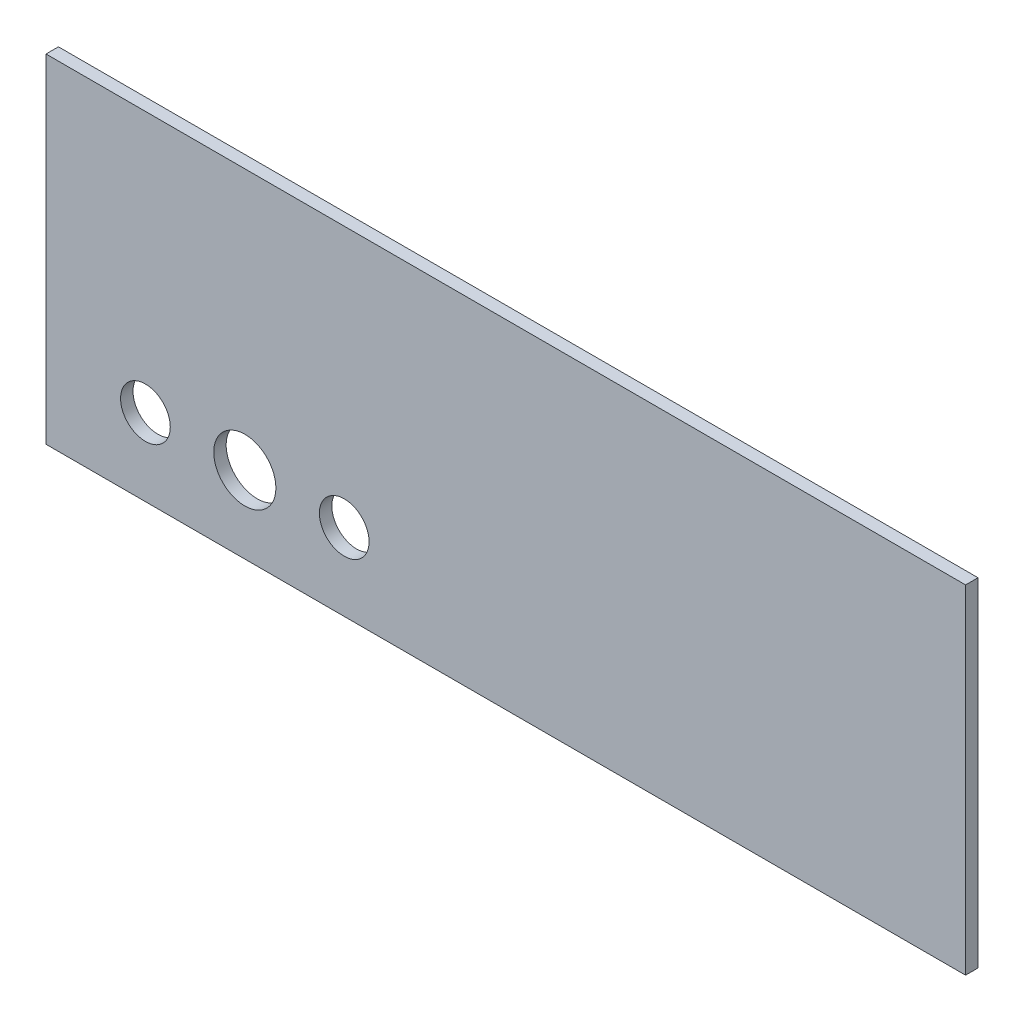
SolidWorks part; units mm, degrees
material "1060 Alloy"
ref_plane "Front Plane" through (0, 0, 0) normal (0, 0, 1) x (1, 0, 0)
ref_plane "Top Plane" through (0, 0, 0) normal (0, 1, 0) x (1, 0, 0)
ref_plane "Right Plane" through (0, 0, 0) normal (1, 0, 0) x (0, 0, -1)
sketch "Sketch1" plane through (0, 0, 0) normal (0, 0, 1) x (1, 0, 0)
  line L1 (-117.475, -43.18) -> (117.475, -43.18)
  line L2 (-117.475, -43.18) -> (-117.475, 43.18)
  line L3 (-117.475, 43.18) -> (117.475, 43.18)
  line L4 (117.475, -43.18) -> (117.475, 43.18)
  line L5 (-117.475, -43.18) -> (117.475, 43.18) construction
  line L6 (-117.475, 43.18) -> (117.475, -43.18) construction
  point P0 (0, 0)
  dimension "D1" = 86.36
  dimension "D2" = 234.95
base flange "Base-Flange1" sketch "Sketch1" thickness 3.175 reverse thickness direction no parameters "D1"=3
edge flange "Edge-Flange1" [suppressed] sketch "Sketch8" flange angle 90 bend radius 3 thickness 3.175
sketch "Sketch8" plane through (0, -43.18, -3.175) normal (0, -1, 0) x (-1, 0, 0)
  line L0 (117.475, 0) -> (-117.475, 0) construction
  line L1 (117.475, 0) -> (-117.475, 0)
  line L2 (-117.475, 0) -> (-117.475, 15.875)
  line L3 (-117.475, 15.875) -> (117.475, 15.875)
  line L4 (117.475, 15.875) -> (117.475, 0)
bend "EdgeBend1" bend radius 3 bend angle 90 parameters "D5"=1, "D6"=10, "D7"=19.05
sketch "Sketch10" [suppressed] plane through (0, -43.18, 0) normal (0, -1, 0) x (1, 0, 0)
  line L0 (-117.475, -19.05) -> (117.475, -19.05) construction
  circle A0 centre (-63.5, -12.7) radius 3.9688
  dimension "D1" = 7.9375
  dimension "D2" = 6.35
extrude "Cut-Extrude2" [suppressed] cut sketch "Sketch10" against normal through all
sketch "Sketch12" [suppressed] plane through (0, -43.18, 0) normal (0, -1, 0) x (1, 0, 0)
  line L0 (-117.475, -3.175) -> (117.475, -3.175) construction
  line L1 (-117.475, -3.175) -> (117.475, -3.175) construction
  line L3 (-117.475, -19.05) -> (-112.649, -19.05)
  line L4 (-117.475, -19.05) -> (-117.475, -3.175)
  line L5 (-117.475, -3.175) -> (-112.649, -3.175)
  line L6 (-112.649, -19.05) -> (-112.649, -3.175)
  dimension "D1" = 4.826
extrude "Cut-Extrude4" [suppressed] cut sketch "Sketch12" against normal through all
mirror "Mirror1" [suppressed] about plane through (0, 0, 0) normal (1, 0, 0)
sketch "Sketch11" plane through (0, 0, 0) normal (0, 0, 1) x (1, 0, 0)
  line L2 (-117.475, 43.18) -> (-117.475, -43.18) construction
  line L4 (117.475, 43.18) -> (-117.475, 43.18) construction
  circle A1 centre (-66.675, -23.495) radius 7.9375
  dimension "D1" = 50.8
  dimension "D4" = 15.875
  dimension "D2" = 66.675
extrude "Cut-Extrude3" cut sketch "Sketch11" against normal through all normal cut yes
sketch "Sketch13" plane through (0, 0, 0) normal (0, 0, 1) x (1, 0, 0)
  circle A0 centre (-41.275, -23.495) radius 6.35
  circle A1 centre (-66.675, -23.495) radius 7.9375 construction
  circle A2 centre (-66.675, -23.495) radius 7.9375 construction
  dimension "D1" = 12.7
  dimension "D2" = 25.4
extrude "Cut-Extrude5" cut sketch "Sketch13" against normal through all normal cut yes
sketch "Sketch14" plane through (0, 0, 0) normal (0, 0, 1) x (1, 0, 0)
  line L0 (-117.475, 43.18) -> (-117.475, -43.18) construction
  circle A0 centre (-92.075, -23.495) radius 6.35
  circle A1 centre (-41.275, -23.495) radius 6.35 construction
  circle A2 centre (-41.275, -23.495) radius 6.35 construction
  dimension "D1" = 12.7
  dimension "D2" = 25.4
extrude "Cut-Extrude6" cut sketch "Sketch14" against normal through all normal cut yes
sketch "Bend-Lines1" [suppressed] plane through (0, 0, 0) normal (0, 1, 0) x (1, 0, 0)
sketch "Bounding-Box1" [suppressed] plane through (0, 0, 0) normal (0, 1, 0) x (1, 0, 0)
sheet metal parameters "Sheet-Metal1" thickness 3.175 parameters "D1"=3
flat pattern "Flat-Pattern1" [suppressed]
sketch "Bend-Lines2" plane through (0, 0, 0) normal (0, 1, 0) x (1, 0, 0)
sketch3d "Bounding-Box2" [suppressed]
  line L0 (117.475, -38.1, 0) -> (-117.475, -38.1, 0) construction
  line L1 (117.475, 38.1, 0) -> (-117.475, 38.1, 0) construction
  line L2 (117.475, -38.1, 0) -> (117.475, 38.1, 0) construction
  line L3 (-117.475, -38.1, 0) -> (-117.475, 38.1, 0) construction
sheet metal parameters "Sheet-Metal2" thickness 3.175 parameters "D1"=3
flat pattern "Flat-Pattern1"
sketch "Bend-Lines2" plane through (0, 0, 0) normal (0, 0, 1) x (1, 0, 0)
  line L0 (-117.475, -35.528) -> (117.475, -35.528) construction
  line L1 (-117.475, -35.528) -> (117.475, -35.528) construction
sketch3d "Bounding-Box2" [suppressed]
  line L0 (-117.475, -52.006, 0) -> (117.475, -52.006, 0) construction
  line L1 (-117.475, 38.1, 0) -> (117.475, 38.1, 0) construction
  line L2 (-117.475, -52.006, 0) -> (-117.475, 38.1, 0) construction
  line L3 (117.475, -52.006, 0) -> (117.475, 38.1, 0) construction
bend of the flat pattern "Flatten-<EdgeBend1>1"
sheet metal parameters "Sheet-Metal5" thickness 3.175 parameters "D1"=3
flat pattern "Flat-Pattern1" [suppressed]
sketch "Bend-Lines2" plane through (0, 0, 0) normal (0, 0, 1) x (1, 0, 0)
  line L0 (-112.7125, -38.703) -> (117.475, -38.703) construction
  line L1 (-112.7125, -38.703) -> (117.475, -38.703) construction
sketch3d "Bounding-Box2" [suppressed]
  line L0 (-117.475, -55.181, 0) -> (117.475, -55.181, 0) construction
  line L1 (-117.475, 41.275, 0) -> (117.475, 41.275, 0) construction
  line L2 (-117.475, -55.181, 0) -> (-117.475, 41.275, 0) construction
  line L3 (117.475, -55.181, 0) -> (117.475, 41.275, 0) construction
bend of the flat pattern "Flatten-<EdgeBend1>1"
sketch "Sketch10-1" [suppressed] plane through (0, -36.131, 0) normal (0, 0, 1) x (1, 0, 0)
  line L0 (-112.7125, -19.05) -> (117.475, -19.05) construction
  line L2 (-117.475, -19.05) -> (-112.7125, -19.05)
  line L3 (-117.475, -19.05) -> (-117.475, -3.175)
  line L4 (-117.475, -3.175) -> (-112.7125, -3.175)
  line L5 (-112.7125, -19.05) -> (-112.7125, -3.175)
  line L8 (-117.475, -3.175) -> (117.475, -3.175) construction
  circle A0 centre (-73.5966, -12.7) radius 3.9688
  dimension "D1" = 7.9375
  dimension "D2" = 6.35
  dimension "D3" = 4.7625
sheet metal parameters "Sheet-Metal9" thickness 3.175 parameters "D1"=3
flat pattern "Flat-Pattern1" [suppressed]
sketch "Bend-Lines2" plane through (0, 0, 0) normal (0, 0, 1) x (1, 0, 0)
  line L0 (-112.7125, -38.703) -> (112.7125, -38.703) construction
  line L1 (-112.7125, -38.703) -> (112.7125, -38.703) construction
sketch3d "Bounding-Box2" [suppressed]
  line L0 (-117.475, -55.181, 0) -> (117.475, -55.181, 0) construction
  line L1 (-117.475, 41.275, 0) -> (117.475, 41.275, 0) construction
  line L2 (-117.475, -55.181, 0) -> (-117.475, 41.275, 0) construction
  line L3 (117.475, -55.181, 0) -> (117.475, 41.275, 0) construction
bend of the flat pattern "Flatten-<EdgeBend1>1"
sketch "Sketch10-1" plane through (0, -36.131, 0) normal (0, 0, 1) x (1, 0, 0)
  line L0 (-112.7125, -19.05) -> (112.7125, -19.05) construction
  line L2 (-117.475, -19.05) -> (-112.7125, -19.05)
  line L3 (-117.475, -19.05) -> (-117.475, -3.175)
  line L4 (-117.475, -3.175) -> (-112.7125, -3.175)
  line L5 (-112.7125, -19.05) -> (-112.7125, -3.175)
  line L8 (-117.475, -3.175) -> (117.475, -3.175) construction
  circle A0 centre (-63.5, -12.7) radius 3.9688
  dimension "D1" = 7.9375
  dimension "D2" = 6.35
  dimension "D3" = 4.7625
  dimension "D4" = 53.975
sheet metal parameters "Sheet-Metal10" thickness 3.175 parameters "D1"=3
flat pattern "Flat-Pattern1" [suppressed]
sketch "Bend-Lines2" plane through (0, 0, 0) normal (0, 0, 1) x (1, 0, 0)
  line L0 (-112.649, -40.608) -> (112.649, -40.608) construction
  line L1 (-112.649, -40.608) -> (112.649, -40.608) construction
sketch3d "Bounding-Box2" [suppressed]
  line L0 (-117.475, -57.086, 0) -> (117.475, -57.086, 0) construction
  line L1 (-117.475, 43.18, 0) -> (117.475, 43.18, 0) construction
  line L2 (-117.475, -57.086, 0) -> (-117.475, 43.18, 0) construction
  line L3 (117.475, -57.086, 0) -> (117.475, 43.18, 0) construction
sketch "Sketch10-1" plane through (0, -38.036, 0) normal (0, 0, 1) x (1, 0, 0)
  line L0 (-112.649, -19.05) -> (112.649, -19.05) construction
  circle A0 centre (-63.5, -12.7) radius 3.9688
  dimension "D1" = 7.9375
  dimension "D2" = 6.35
sheet metal parameters "Sheet-Metal11" thickness 3.175 parameters "D1"=3
flat pattern "Flat-Pattern1" [suppressed]
sketch "Bend-Lines2" plane through (0, 0, 0) normal (0, 0, 1) x (1, 0, 0)
  line L0 (-112.649, -40.608) -> (117.475, -40.608) construction
  line L1 (-112.649, -40.608) -> (117.475, -40.608) construction
sketch3d "Bounding-Box2" [suppressed]
  line L0 (-117.475, -57.086, 0) -> (117.475, -57.086, 0) construction
  line L1 (-117.475, 43.18, 0) -> (117.475, 43.18, 0) construction
  line L2 (-117.475, -57.086, 0) -> (-117.475, 43.18, 0) construction
  line L3 (117.475, -57.086, 0) -> (117.475, 43.18, 0) construction
bend of the flat pattern "Flatten-<EdgeBend1>1"
sketch "Sketch10-1" plane through (0, -38.036, 0) normal (0, 0, 1) x (1, 0, 0)
  line L0 (-112.649, -19.05) -> (117.475, -19.05) construction
  circle A0 centre (-63.5, -12.7) radius 3.9688
  dimension "D1" = 7.9375
  dimension "D2" = 6.35
sheet metal parameters "Sheet-Metal12" thickness 3.175 parameters "D1"=3
flat pattern "Flat-Pattern1" [suppressed]
sketch "Bend-Lines2" plane through (0, 0, 0) normal (0, 0, 1) x (1, 0, 0)
  line L0 (-112.649, -40.608) -> (112.649, -40.608) construction
  line L1 (-112.649, -40.608) -> (112.649, -40.608) construction
sketch3d "Bounding-Box2" [suppressed]
  line L0 (-117.475, -57.086, 0) -> (117.475, -57.086, 0) construction
  line L1 (-117.475, 43.18, 0) -> (117.475, 43.18, 0) construction
  line L2 (-117.475, -57.086, 0) -> (-117.475, 43.18, 0) construction
  line L3 (117.475, -57.086, 0) -> (117.475, 43.18, 0) construction
sketch "Sketch10-1" plane through (0, -38.036, 0) normal (0, 0, 1) x (1, 0, 0)
  line L0 (-112.649, -19.05) -> (112.649, -19.05) construction
  circle A0 centre (-63.5, -12.7) radius 3.9688
  dimension "D1" = 7.9375
  dimension "D2" = 6.35
sheet metal parameters "Sheet-Metal13" thickness 3.175 parameters "D1"=3
flat pattern "Flat-Pattern1"
sketch "Bend-Lines2" plane through (0, 0, 0) normal (0, 0, 1) x (1, 0, 0)
sketch3d "Bounding-Box2" [suppressed]
  line L0 (-117.475, -43.18, 0) -> (117.475, -43.18, 0) construction
  line L1 (-117.475, 43.18, 0) -> (117.475, 43.18, 0) construction
  line L2 (-117.475, -43.18, 0) -> (-117.475, 43.18, 0) construction
  line L3 (117.475, -43.18, 0) -> (117.475, 43.18, 0) construction
